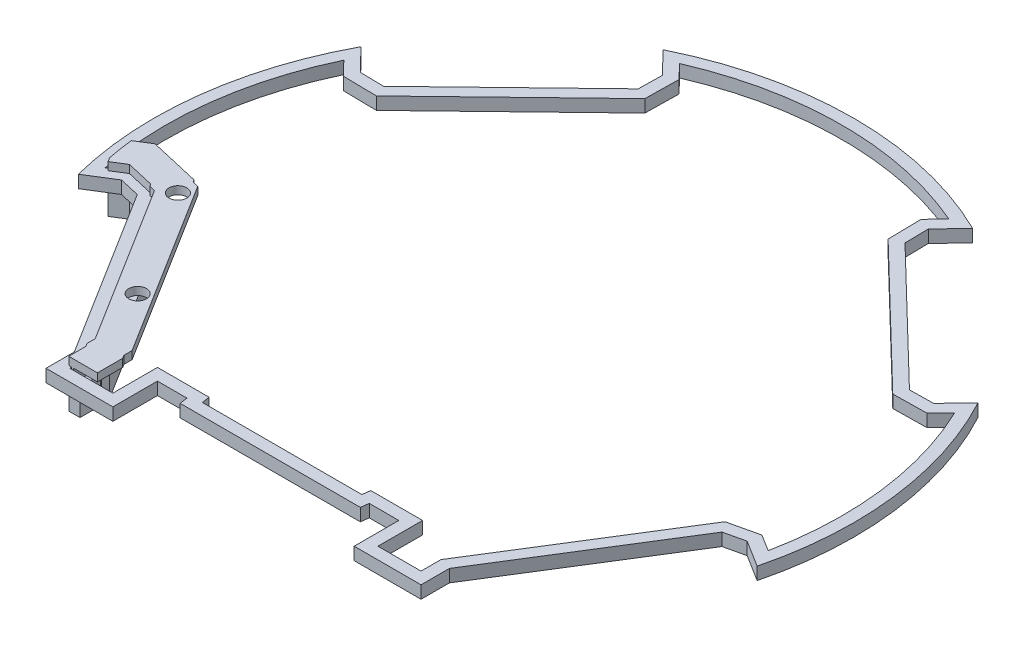
SolidWorks part; units mm, degrees
material "6061 Alloy"
ref_plane "Front Plane" through (0, 0, 0) normal (0, 0, 1) x (1, 0, 0)
ref_plane "Top Plane" through (0, 0, 0) normal (0, 1, 0) x (1, 0, 0)
ref_plane "Right Plane" through (0, 0, 0) normal (1, 0, 0) x (0, 0, -1)
sketch "Sketch1" plane through (0, 0, 0) normal (0, 1, 0) x (1, 0, 0)
  line L0 (0, 0) -> (0, -55.55) construction
  line L1 (-83.4462, -16.178) -> (-71.2857, -8.5793) construction
  line L6 (0, 0) -> (-59.046, 61.1439) construction
  line L7 (0, 0) -> (-72.0841, -45.0431) construction
  line L8 (-33.174, 78.2591) -> (-23.2129, 67.9442) construction
  line L9 (-72.0841, -45.0431) -> (-70.388, -43.9833) construction
  line L10 (-70.388, -43.9833) -> (-84.9608, -20.662) construction
  line L11 (-84.9608, -20.662) -> (-72.2401, -12.7132) construction
  line L12 (-72.2401, -12.7132) -> (-43.0945, -59.3558) construction
  line L13 (-43.0945, -59.3558) -> (-55.8152, -67.3046) construction
  line L14 (-55.8152, -67.3046) -> (-70.388, -43.9833) construction
  line L21 (-59.046, 61.1439) -> (-57.6566, 59.7052)
  line L22 (-77.4385, 40.6021) -> (-37.8748, 78.8083) construction
  line L23 (-73.9694, 32.6911) -> (-77.0537, 35.885)
  line L24 (-37.8748, 78.8083) -> (-27.4549, 68.0182) construction
  line L25 (-27.4549, 68.0182) -> (-67.0186, 29.812) construction
  line L26 (-67.0186, 29.812) -> (-77.4385, 40.6021) construction
  line L27 (-43.0945, -64.8266) -> (-34, -64.8266)
  line L33 (-86.5505, -18.1178) -> (-71.2857, -8.5793) construction
  line L34 (0, 0) -> (0, 50000) construction
  line L35 (0, 0) -> (-50000, 0) construction
  line L36 (-64.3366, -55.55) -> (-19.7189, -55.55) construction
  line L38 (-67.0927, 25.57) -> (-79.5965, 38.5181) construction
  line L39 (-54.9774, -64.8266) -> (0, -64.8266) construction
  line L40 (-35.7168, 80.8923) -> (-23.2129, 67.9442) construction
  line L41 (-38.9606, -60.3102) -> (-54.2255, -69.8488) construction
  line L42 (-34, -55.55) -> (-19.7189, -55.55) construction
  line L43 (-43.0945, -64.8266) -> (-43.0945, -58.4123) construction
  line L45 (73.9694, 32.6911) -> (77.0537, 35.885)
  line L46 (-71.2857, -8.5793) -> (-38.9606, -60.3102) construction
  line L47 (83.4462, -16.178) -> (79.6809, -13.8252)
  line L48 (69.4846, -16.1792) -> (43.8945, -57.132)
  line L50 (43.0945, -64.8266) -> (34, -64.8266)
  line L51 (34, -55.55) -> (34, -64.8266)
  line L52 (0, 0) -> (72.0841, -45.0431) construction
  line L53 (0, 0) -> (59.046, 61.1439) construction
  line L54 (-30.0897, 75.0653) -> (-30.2847, 63.8954)
  line L55 (-62.7996, 32.4961) -> (-30.2847, 63.8954)
  line L56 (-30.0897, 75.0653) -> (-33.174, 78.2591)
  line L57 (73.9694, 32.6911) -> (77.0537, 35.885)
  line L58 (30.0897, 75.0653) -> (33.174, 78.2591)
  line L59 (-34, -55.55) -> (-34, -53.55)
  line L60 (62.7996, 32.4961) -> (30.2847, 63.8954)
  line L61 (-73.9694, 32.6911) -> (-62.7996, 32.4961)
  line L62 (-77.0537, 35.885) -> (-67.0927, 25.57) construction
  line L63 (-83.4462, -16.178) -> (-79.6809, -13.8252)
  line L64 (-79.6809, -13.8252) -> (-69.4846, -16.1792)
  line L65 (-69.4846, -16.1792) -> (-43.8945, -57.132)
  line L66 (-27.4549, 68.0182) -> (-23.2129, 67.9442) construction
  line L67 (-72.2401, -12.7132) -> (-71.2857, -8.5793) construction
  line L68 (30.0897, 75.0653) -> (30.2847, 63.8954)
  line L69 (73.9694, 32.6911) -> (62.7996, 32.4961)
  line L70 (-34, -55.55) -> (-34, -64.8266)
  line L71 (79.6809, -13.8252) -> (69.4846, -16.1792)
  line L72 (-34, -53.55) -> (-20, -53.55)
  line L73 (-20, -53.55) -> (-19.7189, -55.55)
  line L74 (-19.7189, -55.55) -> (19.7189, -55.55)
  line L75 (20, -53.55) -> (19.7189, -55.55)
  line L76 (34, -53.55) -> (20, -53.55)
  line L77 (34, -55.55) -> (34, -53.55)
  line L78 (-43.0945, -64.8266) -> (-43.8945, -64.8266)
  line L79 (-19.7189, -55.55) -> (0, -55.55) construction
  line L80 (-19.7189, -55.55) -> (34, -55.55) construction
  line L81 (-43.8945, -64.8266) -> (-43.8945, -57.132)
  line L82 (-43.0945, -58.4123) -> (-43.8945, -57.132) construction
  line L83 (43.8945, -64.8266) -> (43.8945, -57.132)
  line L84 (43.0945, -64.8266) -> (43.8945, -64.8266)
  line L97 (-23.2129, 67.9442) -> (-67.0927, 25.57) construction
  circle A0 centre (0, 0) radius 85 construction
  circle A1 centre (0, 0) radius 90 construction
  arc A51 (-77.0537, 35.885) -> (-83.4462, -16.178) centre (0, 0) ccw
  arc A52 (77.0537, 35.885) -> (83.4462, -16.178) centre (0, 0) cw
  arc A54 (-33.174, 78.2591) -> (33.174, 78.2591) centre (0, 0) cw
  point P29 (-31.6318, 76.6622)
  point P33 (-47.2368, 48.9151)
  point P34 (31.6318, 76.6622)
  point P35 (-57.6673, -36.0345)
  point P85 (-57.6566, 59.7052)
  dimension "D2" = 58
  dimension "D10" = 82
  dimension "D12" = 170
  dimension "D14" = 34
  dimension "D13" = 2
  dimension "D15" = 3
  dimension "D3" = 180
  dimension "D4" = 64.8266
  dimension "D5" = 44
  dimension "D6" = 15
  dimension "D7" = 55
  dimension "D8" = 55.55
  dimension "D9" = 2
  dimension "D11" = 2
  dimension "D16" = 7
  dimension "D17" = 7
  dimension "D18" = 0.5
  dimension "D19" = 1
  dimension "D20" = 14
  dimension "D21" = 0.8
extrude "Boss-Extrude4" add sketch "Sketch1" along normal mid plane 3.175 contours A0 L70 region at (0, 0, -7.394)
ref_point "Rear_Axle_Center (L)"
ref_axis "Rear_Axle_Proj (L)" through (46.5421, 0, -48.1958) along (0, 1, 0)
ref_point "Front_Axle_Center (L)"
ref_axis "Front_Axle_Proj (L)" [suppressed] through (57.2432, 0, 35.7696) along (0, 1, 0)
ref_point "Front_Axle_Center (R)"
ref_axis "Front_Axle_Proj (R)" through (-57.2432, 0, 35.7696) along (0, 1, 0)
ref_point "Read_Axle_Center (R)"
ref_axis "Rear_Axle_Proj (R)" through (-46.5421, 0, -48.1958) along (0, 1, 0)
sketch "Sketch17" [suppressed] plane through (0, 1.5875, 0) normal (0, 1, 0) x (1, 0, 0)
  line L0 (0, -50.55) -> (0, -55.55) construction
  line L1 (-19.7189, -55.55) -> (19.7189, -55.55) construction
  circle A0 centre (0, -50.55) radius 8.5
  dimension "D1" = 17
  dimension "D2" = 5
extrude "Boss-Extrude5" [suppressed] add sketch "Sketch17" against normal up to surface (3.175 mm away)
ref_plane "Plane1" through (0, 0, 10) normal (0, 0, 1) x (1, 0, 0)
hole_wizard "M3 Clearance Hole4" positions "Sketch9" profile "Sketch10" hole size "M3" standard "ANSI Metric" end condition through all
sketch "Sketch9" plane through (0, -1.5875, 0) normal (0, -1, 0) x (-1, 0, 0)
  line L0 (0, 0) -> (0, 63.4318) construction
  line L1 (-38.0437, 52.9272) -> (38.0437, 52.9272) construction
  line L3 (61.0625, 30.6981) -> (-61.0625, 30.6981) construction
  line L4 (-67.0993, -15.2789) -> (67.0993, -15.2789) construction
  line L5 (50.1419, -42.4164) -> (-50.1419, -42.4164) construction
  line L6 (-61.0625, 30.6981) -> (-38.0437, 52.9272) construction
  line L7 (38.0437, 52.9272) -> (61.0625, 30.6981) construction
  line L8 (67.0993, -15.2789) -> (50.1419, -42.4164) construction
  line L9 (-50.1419, -42.4164) -> (-67.0993, -15.2789) construction
  line L10 (0, 0) -> (-44.8055, 46.3974) construction
  line L11 (0, 0) -> (44.8055, 46.3974) construction
  line L12 (0, 0) -> (-96.9468, 0) construction
  line L14 (-55.1231, -34.4448) -> (0, 0) construction
  line L15 (0, 0) -> (55.1231, -34.4448) construction
  line L18 (-69.4846, -16.1792) -> (-43.8945, -57.132) construction
  line L19 (-62.7996, 32.4961) -> (-30.2847, 63.8954) construction
  point P0 (-67.0993, -15.2789)
  point P2 (-50.1419, -42.4164)
  point P9 (-61.0625, 30.6981)
  point P11 (-38.0437, 52.9272)
  point P30 (50.1419, -42.4164)
  point P31 (67.0993, -15.2789)
  point P32 (38.0437, 52.9272)
  point P33 (61.0625, 30.6981)
  dimension "D9" = 46
  dimension "D10" = 46
  dimension "D11" = 32
  dimension "D12" = 32
  dimension "D7" = 58
  dimension "D5" = 32
  dimension "D6" = 2.5
  dimension "D8" = 9.4
  dimension "D2" = 44
  dimension "D3" = 32
  dimension "D4" = 2.5
  dimension "D13" = 9.4
sketch "Sketch10" plane through (67.0993, -1.5875, 15.2789) normal (1, 0, 0) x (0, 0, -1)
  line L0 (0, 0) -> (0, 3.175)
  line L1 (0, 3.175) -> (1.475, 3.175)
  line L2 (1.475, 3.175) -> (1.475, 0)
  line L5 (1.475, 0) -> (0, 0)
  line L11 (0, -6.35) -> (0, 107.95) construction
  dimension "Thru Hole Dia." = 2.95
  dimension "Thru Hole Depth" = 3.175
sketch "Sketch20" [suppressed] plane through (0, 1.5875, 0) normal (0, 1, 0) x (1, 0, 0)
  line L0 (-16.1485, 44) -> (-16.1485, 39) construction
  line L1 (-14.6485, 44) -> (-14.6485, 39)
  line L2 (-17.6485, 44) -> (-17.6485, 39)
  line L3 (0, 0) -> (0, 85) construction
  line L5 (16.1485, 44) -> (16.1485, 39) construction
  line L6 (14.6485, 44) -> (14.6485, 39)
  line L7 (17.6485, 44) -> (17.6485, 39)
  arc A0 (-14.6485, 44) -> (-17.6485, 44) centre (-16.1485, 44) ccw
  arc A1 (-17.6485, 39) -> (-14.6485, 39) centre (-16.1485, 39) ccw
  arc A5 (33.174, 78.2591) -> (-33.174, 78.2591) centre (0, 0) ccw construction
  arc A7 (14.6485, 44) -> (17.6485, 44) centre (16.1485, 44) cw
  arc A8 (17.6485, 39) -> (14.6485, 39) centre (16.1485, 39) cw
  point P2 (-16.1485, 41.5)
  point P16 (16.1485, 41.5)
  dimension "D1" = 44
  dimension "D2" = 3
  dimension "D3" = 5
  dimension "D4" = 16.1485
extrude "Cut-Extrude1" [suppressed] cut sketch "Sketch20" against normal through all
sketch "Sketch22" plane through (0, 1.5875, 0) normal (0, 1, 0) x (1, 0, 0)
  line L0 (-56.6896, -36.6556) -> (-58.0464, -37.5035) construction
  line L1 (-69.4846, -16.1792) -> (-43.8945, -57.132) construction
  line L2 (-62.9979, 32.9997) -> (-73.7536, 33.1874)
  line L3 (30.2452, 66.1578) -> (65.062, 32.5356)
  line L4 (71.6894, -15.6702) -> (43.8945, -60.1514)
  line L5 (-19.7189, -55.55) -> (19.7189, -55.55) construction
  line L6 (-43.8945, -64.8266) -> (-43.8945, -57.132) construction
  line L7 (-73.7536, 33.1874) -> (-77.1973, 36.7535)
  line L8 (-83.7957, -16.986) -> (-79.5916, -14.359)
  line L9 (-79.5916, -14.359) -> (-69.7989, -16.6198)
  line L10 (-69.7989, -16.6198) -> (-44.3945, -57.2754)
  line L11 (-44.3945, -57.2754) -> (-44.3945, -65.3266)
  line L12 (-44.3945, -65.3266) -> (-33.5, -65.3266)
  line L13 (-33.5, -65.3266) -> (-33.5, -54.05)
  line L14 (-33.5, -54.05) -> (-20.4346, -54.05)
  line L15 (-20.4346, -54.05) -> (-20.1536, -56.05)
  line L16 (-20.1536, -56.05) -> (20.1536, -56.05)
  line L17 (20.1536, -56.05) -> (20.4346, -54.05)
  line L18 (20.4346, -54.05) -> (33.5, -54.05)
  line L19 (33.5, -54.05) -> (33.5, -65.3266)
  line L20 (33.5, -65.3266) -> (44.3945, -65.3266)
  line L21 (44.3945, -65.3266) -> (44.3945, -57.2754)
  line L22 (44.3945, -57.2754) -> (69.7989, -16.6198)
  line L23 (69.7989, -16.6198) -> (79.5916, -14.359)
  line L24 (79.5916, -14.359) -> (83.7957, -16.986)
  line L25 (77.1973, 36.7535) -> (73.7536, 33.1874)
  line L26 (73.7536, 33.1874) -> (62.9979, 32.9997)
  line L27 (62.9979, 32.9997) -> (30.781, 64.1112)
  line L28 (-30.2452, 66.1578) -> (-65.062, 32.5356)
  line L29 (-71.6894, -15.6702) -> (-43.8945, -60.1514)
  line L30 (-79.6809, -13.8252) -> (-69.4846, -16.1792) construction
  line L31 (0, 85) -> (0, -55.55) construction
  line L32 (-46.5421, 48.1958) -> (-47.6536, 49.3467) construction
  line L33 (30.781, 64.1112) -> (30.5932, 74.8669)
  line L34 (30.5932, 74.8669) -> (34.037, 78.433)
  line L35 (-34.037, 78.433) -> (-30.5932, 74.8669)
  line L36 (-30.5932, 74.8669) -> (-30.781, 64.1112)
  line L37 (-20, -53.55) -> (-19.7189, -55.55)
  line L38 (-20, -53.55) -> (-19.7189, -55.55)
  line L40 (-43.8945, -57.132) -> (-43.8945, -64.8266)
  line L41 (-43.8945, -57.132) -> (-43.8945, -64.8266)
  line L43 (43.8945, -64.8266) -> (43.8945, -57.132)
  line L44 (43.8945, -64.8266) -> (43.8945, -57.132)
  line L45 (-30.781, 64.1112) -> (-62.9979, 32.9997)
  line L46 (-85.782, -21.7647) -> (-79.0556, -17.5616)
  line L47 (-79.0556, -17.5616) -> (-73.8893, -18.7544)
  line L49 (-47.3945, -61.155) -> (-47.3945, -68.3266)
  line L50 (-47.3945, -68.3266) -> (-30.5, -68.3266)
  line L51 (-30.5, -68.3266) -> (-30.5, -57.05)
  line L52 (-30.5, -57.05) -> (-23.0425, -57.05)
  line L53 (-23.0425, -57.05) -> (-22.7614, -59.05)
  line L54 (-22.7614, -59.05) -> (22.7614, -59.05)
  line L55 (22.7614, -59.05) -> (23.0425, -57.05)
  line L56 (-19.7189, -55.55) -> (-6.8739, -55.55)
  line L57 (23.0425, -57.05) -> (30.5, -57.05)
  line L58 (19.7189, -55.55) -> (20, -53.55)
  line L59 (20, -53.55) -> (34, -53.55)
  line L60 (34, -53.55) -> (34, -64.8266)
  line L61 (34, -64.8266) -> (43.8945, -64.8266)
  line L62 (30.5, -57.05) -> (30.5, -68.3266)
  line L63 (43.8945, -57.132) -> (69.4846, -16.1792)
  line L64 (69.4846, -16.1792) -> (79.6809, -13.8252)
  line L65 (79.6809, -13.8252) -> (83.4462, -16.178)
  line L66 (77.0537, 35.885) -> (73.9694, 32.6911)
  line L67 (73.9694, 32.6911) -> (62.7996, 32.4961)
  line L68 (62.7996, 32.4961) -> (30.2847, 63.8954)
  line L69 (30.2847, 63.8954) -> (30.0897, 75.0653)
  line L70 (30.0897, 75.0653) -> (33.174, 78.2591)
  line L71 (-33.174, 78.2591) -> (-30.0897, 75.0653)
  line L72 (-30.0897, 75.0653) -> (-30.2847, 63.8954)
  line L73 (-30.2847, 63.8954) -> (-62.7996, 32.4961)
  line L74 (-62.7996, 32.4961) -> (-73.9694, 32.6911)
  line L75 (-73.9694, 32.6911) -> (-77.0537, 35.885)
  line L76 (-83.4462, -16.178) -> (-79.6809, -13.8252)
  line L77 (-79.6809, -13.8252) -> (-69.4846, -16.1792)
  line L78 (-69.4846, -16.1792) -> (-43.8945, -57.132)
  line L79 (30.5, -68.3266) -> (47.3945, -68.3266)
  line L80 (-43.8945, -64.8266) -> (-34, -64.8266)
  line L81 (-34, -64.8266) -> (-34, -53.55)
  line L82 (-34, -53.55) -> (-20, -53.55)
  line L83 (47.3945, -68.3266) -> (47.3945, -61.155)
  line L84 (-19.7189, -55.55) -> (-6.8739, -55.55)
  line L86 (19.7189, -55.55) -> (20, -53.55)
  line L87 (20, -53.55) -> (34, -53.55)
  line L88 (34, -53.55) -> (34, -64.8266)
  line L89 (34, -64.8266) -> (43.8945, -64.8266)
  line L91 (43.8945, -57.132) -> (69.4846, -16.1792)
  line L92 (69.4846, -16.1792) -> (79.6809, -13.8252)
  line L93 (79.6809, -13.8252) -> (83.4462, -16.178)
  line L94 (77.0537, 35.885) -> (73.9694, 32.6911)
  line L95 (73.9694, 32.6911) -> (62.7996, 32.4961)
  line L96 (62.7996, 32.4961) -> (30.2847, 63.8954)
  line L97 (30.2847, 63.8954) -> (30.0897, 75.0653)
  line L98 (30.0897, 75.0653) -> (33.174, 78.2591)
  line L99 (-33.174, 78.2591) -> (-30.0897, 75.0653)
  line L100 (-30.0897, 75.0653) -> (-30.2847, 63.8954)
  line L101 (-30.2847, 63.8954) -> (-62.7996, 32.4961)
  line L102 (-62.7996, 32.4961) -> (-73.9694, 32.6911)
  line L103 (-73.9694, 32.6911) -> (-77.0537, 35.885)
  line L104 (-83.4462, -16.178) -> (-79.6809, -13.8252)
  line L105 (-79.6809, -13.8252) -> (-69.4846, -16.1792)
  line L106 (-69.4846, -16.1792) -> (-43.8945, -57.132)
  line L108 (-43.8945, -64.8266) -> (-34, -64.8266)
  line L109 (-34, -64.8266) -> (-34, -53.55)
  line L110 (-34, -53.55) -> (-20, -53.55)
  line L112 (73.8893, -18.7544) -> (79.0556, -17.5616)
  line L113 (79.0556, -17.5616) -> (85.782, -21.7647)
  line L114 (77.9685, 41.8707) -> (72.4588, 36.1653)
  line L115 (72.4588, 36.1653) -> (66.4504, 36.0604)
  line L117 (33.7193, 67.6684) -> (33.6145, 73.6768)
  line L118 (33.6145, 73.6768) -> (39.1242, 79.3823)
  line L119 (-39.1242, 79.3823) -> (-33.6145, 73.6768)
  line L120 (-33.6145, 73.6768) -> (-33.7193, 67.6684)
  line L122 (-66.4504, 36.0604) -> (-72.4588, 36.1653)
  line L123 (-72.4588, 36.1653) -> (-77.9685, 41.8707)
  line L124 (-30.7415, 66.3736) -> (-65.4093, 32.8953)
  line L125 (-72.0037, -16.1108) -> (-44.3945, -60.2947)
  line L126 (-33.7193, 67.6684) -> (-66.4504, 36.0604)
  line L127 (-73.8893, -18.7544) -> (-47.3945, -61.155)
  line L128 (30.7415, 66.3736) -> (65.2603, 33.0392)
  line L129 (72.0037, -16.1108) -> (44.3945, -60.2947)
  line L130 (73.8893, -18.7544) -> (47.3945, -61.155)
  line L131 (33.7193, 67.6684) -> (66.4504, 36.0604)
  line L132 (-32.6765, 68.6755) -> (-67.4933, 35.0533) construction
  line L133 (-30.5925, 66.5175) -> (-65.4093, 32.8953) construction
  line L134 (-64.188, 36.0209) -> (-72.4588, 36.1653) construction
  line L135 (-33.7588, 65.406) -> (-64.188, 36.0209) construction
  line L136 (-33.6145, 73.6768) -> (-33.7588, 65.406) construction
  line L137 (-74.6576, -17.5249) -> (-46.8627, -62.0061) construction
  line L138 (-79.0556, -17.5616) -> (-71.6846, -19.2634) construction
  line L139 (-71.6846, -19.2634) -> (-47.3945, -58.1356) construction
  line L140 (-47.3945, -58.1356) -> (-47.3945, -68.3266) construction
  line L141 (-72.1134, -15.9352) -> (-44.3185, -60.4163) construction
  line L142 (74.6576, -17.5249) -> (46.8627, -62.0061) construction
  line L143 (47.3945, -68.3266) -> (47.3945, -58.1356) construction
  line L144 (47.3945, -58.1356) -> (71.6846, -19.2634) construction
  line L145 (72.1134, -15.9352) -> (44.3185, -60.4163) construction
  line L146 (71.6846, -19.2634) -> (79.0556, -17.5616) construction
  line L147 (32.6765, 68.6755) -> (67.4933, 35.0533) construction
  line L148 (72.4588, 36.1653) -> (64.188, 36.0209) construction
  line L149 (64.188, 36.0209) -> (33.7588, 65.406) construction
  line L150 (30.5925, 66.5175) -> (65.4093, 32.8953) construction
  line L151 (33.7588, 65.406) -> (33.6145, 73.6768) construction
  arc A0 (-77.1973, 36.7535) -> (-83.7957, -16.986) centre (0, 0) ccw
  arc A1 (83.7957, -16.986) -> (77.1973, 36.7535) centre (0, 0) ccw
  arc A2 (34.037, 78.433) -> (-34.037, 78.433) centre (0, 0) ccw
  arc A3 (-77.9685, 41.8707) -> (-85.782, -21.7647) centre (0, 0) ccw
  arc A4 (85.782, -21.7647) -> (77.9685, 41.8707) centre (0, 0) ccw
  arc A7 (39.1242, 79.3823) -> (-39.1242, 79.3823) centre (0, 0) ccw
  arc A9 (83.4462, -16.178) -> (77.0537, 35.885) centre (0, 0) ccw
  arc A10 (33.174, 78.2591) -> (-33.174, 78.2591) centre (0, 0) ccw
  arc A11 (-77.0537, 35.885) -> (-83.4462, -16.178) centre (0, 0) ccw
  arc A13 (83.4462, -16.178) -> (77.0537, 35.885) centre (0, 0) ccw
  arc A14 (33.174, 78.2591) -> (-33.174, 78.2591) centre (0, 0) ccw
  arc A15 (-77.0537, 35.885) -> (-83.4462, -16.178) centre (0, 0) ccw
  dimension "D2" = 1.6
  dimension "D1" = 0
  dimension "D3" = 0.5
  dimension "D4" = 3
  dimension "D5" = 0.5
  dimension "D6" = 3
  dimension "D7" = 0.5
  dimension "D8" = 3
extrude "Boss-Extrude6" add sketch "Sketch22" against normal up to surface (3.175 mm away) contours L102 L101 L100 L28 | L106 L105 L29 | L92 L91 L4 | L97 L96 L95 L3 region at (-46.7518, 1.5875, -48.4129) region at (-56.7712, 1.5875, 37.103) region at (46.7518, 1.5875, -48.4129) region at (56.7712, 1.5875, 37.103) up to face at (67.0993, -1.5875, 13.8039)
extrude "Boss-Extrude7" add sketch "Sketch22<3>" against normal blind 3.175 separate body contours L118 A7 L119 L120 L126 L122 L123 A3 L46 L47 L127 L49 L50 L51 L52 L53 L54 L55 L57 L62 L79 L83 L130 L112 L113 A4 L114 L115 L131 L117 A2 L34 L33 L128 L26 L25 A1 L24 L23 L129 L21 L20 L19 L18 L17 L16 L15 L14 L13 L12 region at (-85.4931, 1.5875, -10.4972)
sketch "Sketch22<3>" plane through (0, 1.5875, 0) normal (0, 1, 0) x (1, 0, 0) same geometry as "Sketch22"
sketch "Sketch27" plane through (0, 1.5875, 0) normal (0, 1, 0) x (1, 0, 0)
  line L0 (-43.8945, -64.8266) -> (-43.8945, -60.1514)
  line L1 (-43.8945, -64.8266) -> (-43.8945, -57.132) construction
  line L2 (-43.8945, -60.1514) -> (-44.3945, -59.3512)
  line L3 (-44.3945, -59.3512) -> (-43.8945, -60.1514) construction
  line L4 (-44.3945, -59.3512) -> (-44.3945, -57.2754)
  line L5 (-44.3945, -57.2754) -> (-69.7989, -16.6198)
  line L6 (-69.7989, -16.6198) -> (-71.3147, -16.2699)
  line L7 (-71.3147, -16.2699) -> (-71.6894, -15.6702)
  line L8 (-71.6894, -15.6702) -> (-79.6809, -13.8252)
  line L9 (-79.6809, -13.8252) -> (-83.4462, -16.178)
  line L10 (-45.1445, -64.8266) -> (-45.1445, -60.5098)
  line L11 (-45.1445, -60.5098) -> (-45.6445, -59.7096)
  line L12 (-45.6445, -59.7096) -> (-45.6445, -57.6338)
  line L13 (-45.6445, -57.6338) -> (-70.5846, -17.7213)
  line L14 (-70.5846, -17.7213) -> (-72.1004, -17.3714)
  line L15 (-72.1004, -17.3714) -> (-72.4751, -16.7717)
  line L16 (-72.4751, -16.7717) -> (-79.4576, -15.1597)
  line L17 (-79.4576, -15.1597) -> (-82.7838, -17.2381)
  line L18 (-43.8945, -64.8266) -> (-45.1445, -64.8266)
  line L19 (-82.7838, -17.2381) -> (-83.4462, -16.178)
  line L20 (-80.7528, -7.4199) -> (-84.4418, -9.7251)
  line L31 (-37.8945, -64.8266) -> (-37.8945, -58.4309)
  line L32 (-37.8945, -58.4309) -> (-38.3945, -57.6307)
  line L33 (-38.3945, -57.6307) -> (-38.3945, -55.5549)
  line L34 (-38.3945, -55.5549) -> (-66.0276, -11.3327)
  line L35 (-66.0276, -11.3327) -> (-67.5434, -10.9827)
  line L36 (-67.5434, -10.9827) -> (-67.9181, -10.3831)
  line L37 (-67.9181, -10.3831) -> (-80.7528, -7.4199)
  line L38 (-42.2945, -60.4266) -> (-42.2945, -59.6926) construction
  line L39 (-43.8945, -64.8266) -> (-37.8945, -64.8266)
  line L40 (-34, -64.8266) -> (-43.8945, -64.8266) construction
  line L41 (-37.8945, -70.8266) -> (-37.8945, -58.4309) construction
  line L42 (-51.1445, -70.8266) -> (-51.1445, -62.2303) construction
  line L43 (-37.8945, -70.8266) -> (-51.1445, -70.8266) construction
  line L44 (-51.6445, -61.4301) -> (-51.6445, -59.3543) construction
  line L45 (-51.6445, -59.3543) -> (-74.3559, -23.0085) construction
  line L46 (-51.1445, -62.2303) -> (-51.6445, -61.4301) construction
  line L47 (-80.7528, -7.4199) -> (-91.714, -14.2693) construction
  line L48 (-84.6926, -25.5059) -> (-91.714, -14.2693) construction
  line L49 (-78.3857, -21.5649) -> (-84.6926, -25.5059) construction
  line L50 (-74.3559, -23.0085) -> (-75.8717, -22.6585) construction
  line L51 (-76.2464, -22.0588) -> (-78.3857, -21.5649) construction
  line L52 (-75.8717, -22.6585) -> (-76.2464, -22.0588) construction
  line L53 (-42.2945, -64.8266) -> (-42.2945, -59.6926)
  line L54 (-42.2945, -59.6926) -> (-42.7945, -58.8924)
  line L55 (-42.7945, -58.8924) -> (-42.7945, -56.8166)
  line L56 (-42.7945, -56.8166) -> (-68.7932, -15.2099)
  line L57 (-68.7932, -15.2099) -> (-70.309, -14.86)
  line L58 (-70.309, -14.86) -> (-70.6837, -14.2603)
  line L59 (-70.6837, -14.2603) -> (-79.6736, -12.1848)
  line L60 (-79.6736, -12.1848) -> (-79.6736, -12.1848)
  line L61 (-43.8945, -60.4266) -> (-42.2945, -60.4266) construction
  line L62 (-79.6736, -12.1848) -> (-83.7172, -14.7115)
  line L63 (-70.0672, -14.7751) -> (-50.9902, -45.3048) construction
  line L64 (-69.9389, -35.9201) -> (-46.5256, -21.2899) construction
  arc A0 (-77.0537, 35.885) -> (-83.4462, -16.178) centre (0, 0) ccw construction
  arc A1 (-84.4418, -9.7251) -> (-83.4462, -16.178) centre (0, 0) ccw
  circle A2 centre (-50.1419, -42.4164) radius 2.25
  circle A3 centre (-67.0993, -15.2789) radius 2.25
  arc A5 (-79.6736, -12.1848) -> (-79.1266, -15.3406) centre (0, 0) ccw construction
  point P80 (-60.5287, -30.04)
  dimension "D3" = 4.5
  dimension "D4" = 1.6
  dimension "D5" = 36
  dimension "D1" = 1.25
  dimension "D2" = 6
extrude "Boss-Extrude8" add sketch "Sketch27" along normal blind 2 separate body contours L20 A1 L9 L8 L7 L6 L5 L4 L2 L0 L39 L31 L32 L33 L34 L35 L36 L37 A3 A2 | L19 L17 L16 L15 L14 L13 L12 L11 L10 L18 L0 L2 L4 L5 L6 L7 L8 L9 | A3 L57 L58 L59 L62 A1 L9 L8 L7 L6 L5 L4 L2 L0 L39 L53 L54 L55 L56 A2 region at (-44.5195, 1.5875, 64.1812) region at (-43.2246, 1.5875, 62.489) region at (-57.5035, 1.5875, 32.4077)
delete or keep bodies "Body-Delete/Keep 1" type delete bodies bodies 137
extrude "Boss-Extrude9" add sketch "Sketch27<3>" against normal blind 10 contours L19 L17 L16 L15 L14 L13 L12 L11 L10 L18 L0 L2 L4 L5 L6 L7 L8 L9 region at (-44.5195, 1.5875, 64.1812)
sketch "Sketch27<3>" plane through (0, 1.5875, 0) normal (0, 1, 0) x (1, 0, 0) same geometry as "Sketch27"
extrude "Boss-Extrude11" add sketch "Sketch27<7>" against normal up to surface (10 mm away) from offset 3.2 contours A3 L57 L58 L59 L62 A1 L9 L8 L7 L6 L5 L4 L2 L0 L39 L53 L54 L55 L56 A2 region at (-43.2246, 1.5875, 62.489) up to face at (-61.7493, -8.4125, 35.9505) offset against normal yes
sketch "Sketch27<7>" plane through (0, 1.5875, 0) normal (0, 1, 0) x (1, 0, 0) same geometry as "Sketch27"
fillet "Fillet1" [suppressed] radius 2
fillet "Fillet3" [suppressed] radius 1
sketch "Sketch23" [suppressed] plane through (0, 3.175, 0) normal (0, 1, 0) x (1, 0, 0)
  circle A0 centre (0, -53.55) radius 4.95
  dimension "D1" = 9.9
extrude "Cut-Extrude2" [suppressed] cut sketch "Sketch23" against normal through all
sketch "Sketch26" [suppressed] plane through (0, 3.175, 0) normal (0, 1, 0) x (1, 0, 0)
  line L0 (0, 0) -> (0, 50) construction
  line L1 (-92.5, 5) -> (92.5, 5)
  line L2 (-92.5, 5) -> (-92.5, 95)
  line L3 (-92.5, 95) -> (92.5, 95)
  line L4 (92.5, 5) -> (92.5, 95)
  line L5 (-92.5, 5) -> (92.5, 95) construction
  line L6 (-92.5, 95) -> (92.5, 5) construction
  point P0 (0, 50)
  dimension "D1" = 90
  dimension "D2" = 185
  dimension "D3" = 5
extrude "Cut-Extrude3" [suppressed] cut sketch "Sketch26" against normal through all
fillet "Fillet4" [suppressed] radius 5
equation "\"D3@Sketch9\"=\"D5@Sketch9\""
equation "\"D4@Sketch9\"=\"D6@Sketch9\""
equation "\"D13@Sketch9\"=\"D8@Sketch9\""
